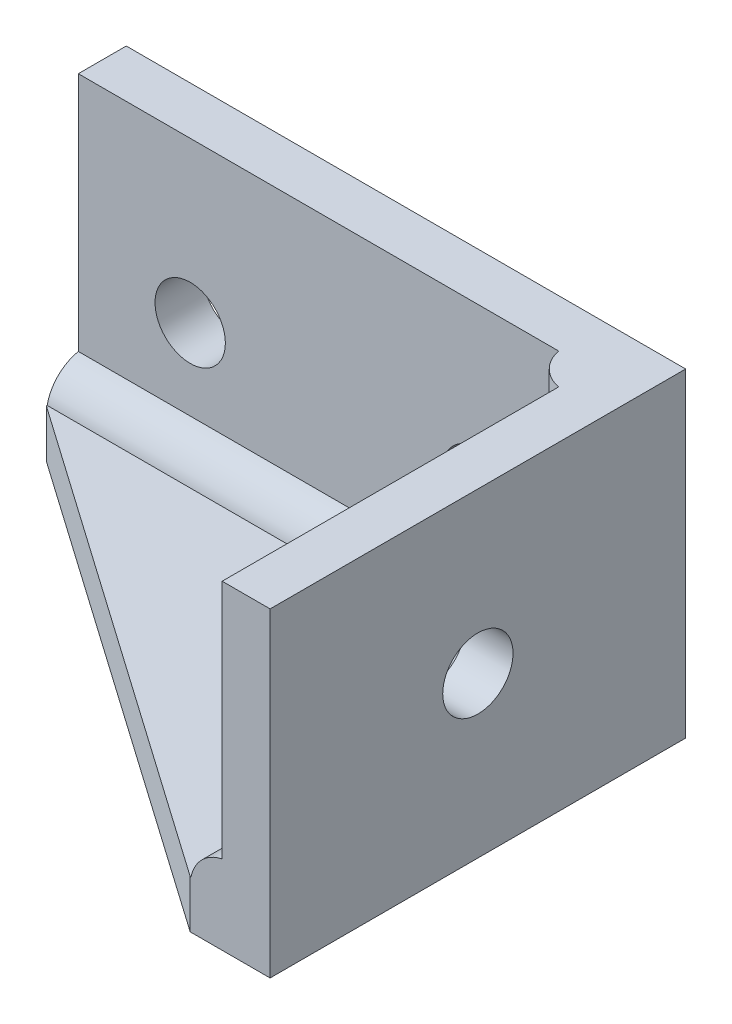
SolidWorks part; units mm, degrees
material "ABS"
ref_plane "Front Plane" through (0, 0, 0) normal (0, 0, 1) x (1, 0, 0)
ref_plane "Top Plane" through (0, 0, 0) normal (0, 1, 0) x (1, 0, 0)
ref_plane "Right Plane" through (0, 0, 0) normal (1, 0, 0) x (0, 0, -1)
sketch "Sketch1" plane through (0, 0, 0) normal (0, 1, 0) x (1, 0, 0)
  line L0 (0, 0) -> (-35, 0)
  line L1 (-35, 0) -> (-35, -5)
  line L2 (-35, -5) -> (-5, -26)
  line L3 (-5, -26) -> (0, -26)
  line L4 (0, -26) -> (0, 0)
  dimension "D1" = 35
  dimension "D2" = 26
  dimension "D3" = 5
  dimension "D4" = 5
extrude "Boss-Extrude1" add sketch "Sketch1" along normal blind 20
sketch "Sketch2" plane through (0, 20, 0) normal (0, 1, 0) x (1, 0, 0)
  line L0 (-35, -3) -> (-3, -3)
  line L1 (-35, 0) -> (-35, -5) construction
  line L2 (-3, -3) -> (-3, -26)
  line L3 (-5, -26) -> (0, -26) construction
  line L4 (-3, -26) -> (-5, -26)
  line L5 (-5, -26) -> (-35, -5)
  line L6 (-35, -5) -> (-35, -3)
  line L7 (0, 0) -> (-35, 0) construction
  line L8 (0, -26) -> (0, 0) construction
  dimension "D1" = 3
  dimension "D2" = 3
extrude "Cut-Extrude1" cut sketch "Sketch2" against normal blind 17
sketch "Sketch3" plane through (0, 0, 26) normal (0, 0, 1) x (1, 0, 0)
  line L2 (0, 20) -> (0, 0) construction
  line L3 (-5, 0) -> (0, 0) construction
  circle A0 centre (-2.5, 2.5) radius 2.5
  dimension "D1" = 5
extrude "Boss-Extrude2" add sketch "Sketch3" against normal up to surface (23 mm away) up to face at (-19, 11.5, 3)
sketch "Sketch4" plane through (-35, 0, 0) normal (-1, 0, 0) x (0, 0, 1)
  line L0 (0, 0) -> (5, 0) construction
  line L1 (0, 20) -> (0, 0) construction
  circle A0 centre (2.5, 2.5) radius 2.5
  dimension "D1" = 5
extrude "Boss-Extrude3" add sketch "Sketch4" against normal up to surface (32 mm away) up to face at (-3, 12.4747, 14.5)
sketch "Sketch5" plane through (0, 20, 0) normal (0, 1, 0) x (1, 0, 0)
  line L0 (0, 0) -> (-35, 0) construction
  line L1 (0, -26) -> (0, 0) construction
  circle A0 centre (-2.5, -2.5) radius 2.5
  dimension "D1" = 5
extrude "Boss-Extrude4" add sketch "Sketch5" against normal up to next
sketch "Sketch6" plane through (0, 0, 3) normal (0, 0, 1) x (1, 0, 0)
  line L0 (-4.9495, 20) -> (-35, 20) construction
  line L1 (-35, 4.9495) -> (-35, 20) construction
  circle A0 centre (-28, 10) radius 2.2
  circle A1 centre (-10, 10) radius 2.2
  dimension "D1" = 4.4
  dimension "D2" = 18
  dimension "D3" = 10
  dimension "D4" = 7
extrude "Cut-Extrude2" cut sketch "Sketch6" against normal through all
sketch "Sketch7" plane through (-3, 0, 0) normal (-1, 0, 0) x (0, 0, 1)
  line L0 (26, 20) -> (4.9495, 20) construction
  line L1 (26, 4.9495) -> (26, 20) construction
  circle A0 centre (13, 10) radius 2.2
  dimension "D1" = 4.4
  dimension "D2" = 10
  dimension "D3" = 13
extrude "Cut-Extrude3" cut sketch "Sketch7" against normal through all
